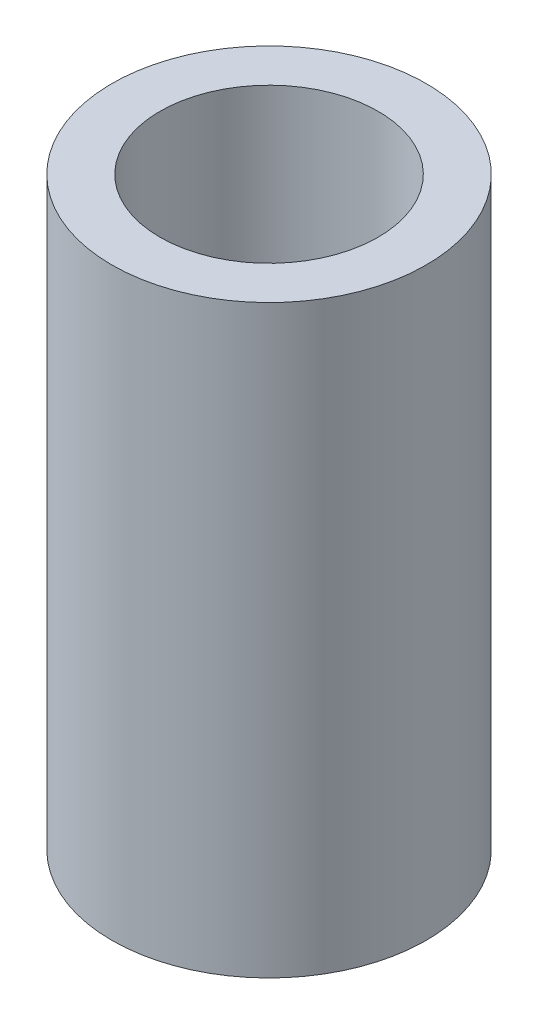
SolidWorks part; units mm, degrees
ref_plane "Front Plane" through (0, 0, 0) normal (0, 0, 1) x (1, 0, 0)
ref_plane "Top Plane" through (0, 0, 0) normal (0, 1, 0) x (1, 0, 0)
ref_plane "Right Plane" through (0, 0, 0) normal (1, 0, 0) x (0, 0, -1)
sketch "Sketch1" plane through (0, 0, 0) normal (0, 1, 0) x (1, 0, 0)
  circle A0 centre (0, 0) radius 12.5
  dimension "SLEEVE_OD" = 25
extrude "Boss-Extrude1" add sketch "Sketch1" along normal blind 46.5233
sketch "Sketch2" plane through (0, 0, 0) normal (0, 1, 0) x (1, 0, 0)
  circle A0 centre (0, 0) radius 8.6777
  dimension "BORE_D" = 17.3554
extrude "Cut-Extrude1" cut sketch "Sketch2" along normal through all
chamfer "Chamfer1" distance 1.6024 angle 61.715 rebuild error yes
